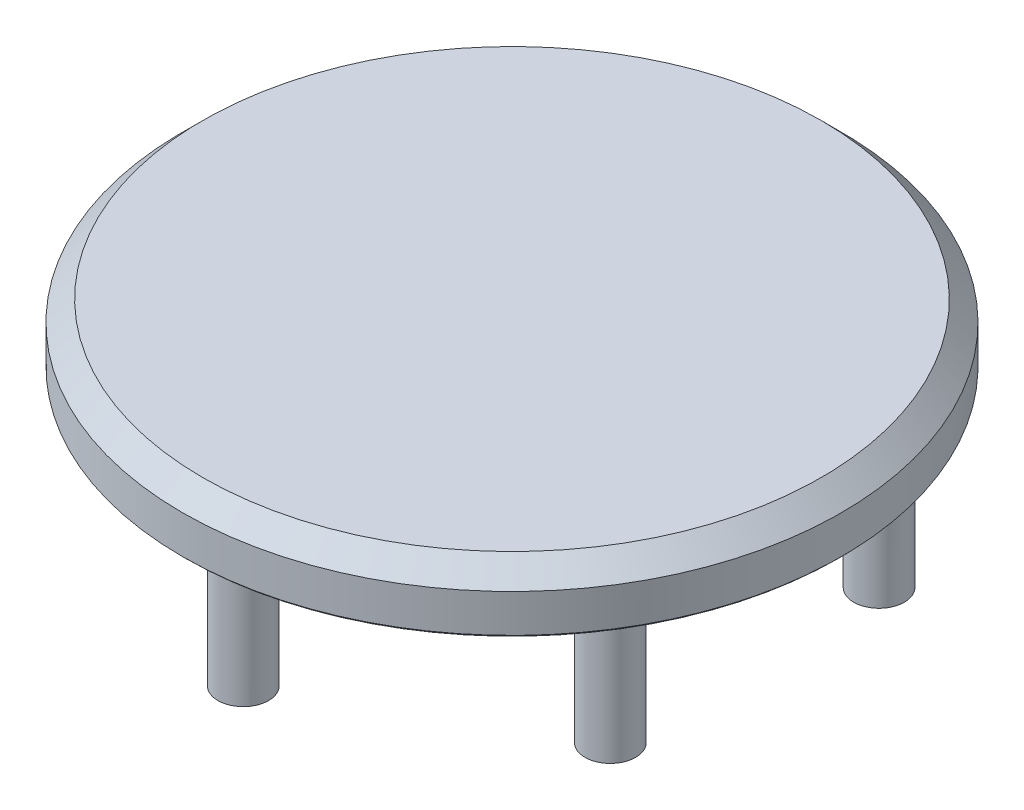
SolidWorks part; units mm, degrees
ref_plane "Front Plane" through (0, 0, 0) normal (0, 0, 1) x (1, 0, 0)
ref_plane "Top Plane" through (0, 0, 0) normal (0, 1, 0) x (1, 0, 0)
ref_plane "Right Plane" through (0, 0, 0) normal (1, 0, 0) x (0, 0, -1)
ref_axis "Axis1" through (0, 0, 0) along (0, 1, 0)
sketch "Sketch3" plane through (0, 0, 0) normal (1, 0, 0) x (0, 0, -1)
  line L0 (0, 0) -> (0, -101510.3777) construction
  line L1 (0, 25) -> (-32.5, 25)
  line L2 (-32.5, 25) -> (-32.5, 31)
  line L3 (-32.5, 31) -> (0, 31)
  line L7 (0, 31) -> (0, 25)
  dimension "D1" = 6
  dimension "D6" = 65
  dimension "D7" = 25
revolve "Revolve1" add sketch "Sketch3" angle 360 about L0
chamfer "Chamfer2" distance 2 angle 45 1 edges at (0, 31, 32.5)
sketch "Sketch4" plane through (0, 25, 0) normal (0, -1, 0) x (1, 0, 0)
  circle A0 centre (0, 26.5) radius 2.5
  dimension "D1" = 5
  dimension "D2" = 26.5
extrude "Boss-Extrude1" add sketch "Sketch4" along normal up to surface (13.8 mm away)
pattern_circular "CirPattern1" count 6 over 360 about axis through (0, 0, 0) along (0, 1, 0) of "Boss-Extrude1"
chamfer "Chamfer3" distance 2 angle 45 6 edges at (0, 25, 24) (-20.7846, 25, 12) (-20.7846, 25, -12) (0, 25, -24) (20.7846, 25, -12) (20.7846, 25, 12)
chamfer "Chamfer4" distance 0.25 angle 45 1 edges at (0, 25, 32.5)
